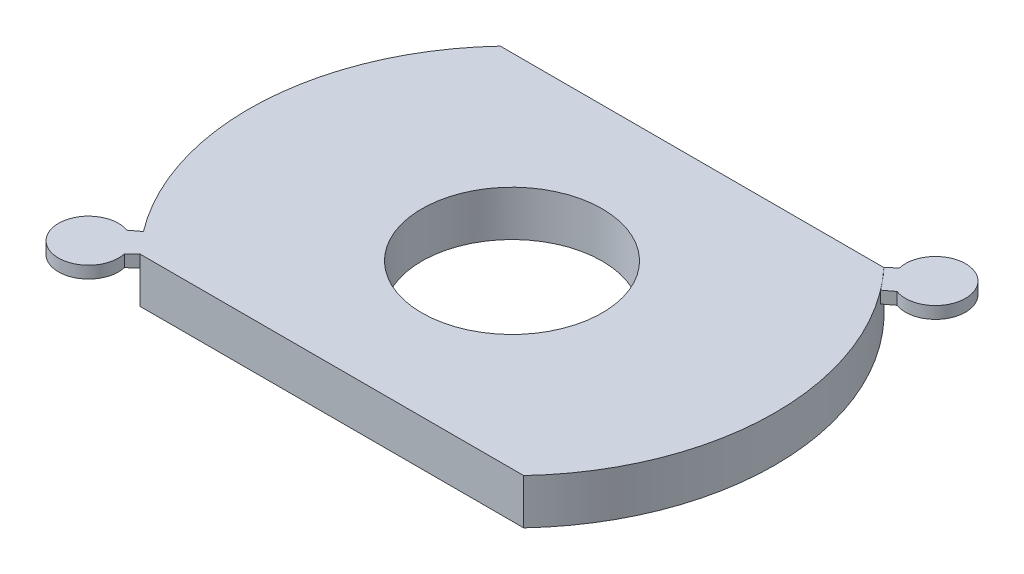
SolidWorks part; units mm, degrees
material "1345 Alloy"
ref_plane "Front Plane" through (0, 0, 0) normal (0, 0, 1) x (1, 0, 0)
ref_plane "Top Plane" through (0, 0, 0) normal (0, 1, 0) x (1, 0, 0)
ref_plane "Right Plane" through (0, 0, 0) normal (1, 0, 0) x (0, 0, -1)
sketch "Sketch1" plane through (0, 0, 0) normal (0, 1, 0) x (1, 0, 0)
  line L0 (-1712.4333, 578.2677) -> (-1658.0172, 559.892) construction
  line L1 (-1682.6566, 611.2885) -> (-1644.8226, 597.5438) construction
  line L2 (-1769.951, 660.0706) -> (-1712.4333, 741.8735) construction
  circle A0 centre (0, 0) radius 1750
  arc A3 (-1712.4333, 578.2677) -> (-1712.4333, 741.8735) centre (-1769.951, 660.0706) cw construction
  arc A4 (-1712.4333, 741.8735) -> (-1682.6566, 611.2885) centre (-1769.951, 660.0706) cw construction
extrude "Boss-Extrude1" add sketch "Sketch1" along normal blind 500
sketch "Sketch2" plane through (0, 500, 0) normal (0, 1, 0) x (1, 0, 0)
  circle A0 centre (0, 0) radius 900
extrude "Cut-Extrude2" cut sketch "Sketch2" against normal blind 300
sketch "Sketch9" plane through (0, 0, 0) normal (0, -1, 0) x (1, 0, 0)
  line L1 (-2106.3119, -1198.0599) -> (2106.3119, -1198.0599)
  line L2 (-2106.3119, -1198.0599) -> (-2106.3119, 1198.0599)
  line L3 (-2106.3119, 1198.0599) -> (2106.3119, 1198.0599)
  line L4 (2106.3119, -1198.0599) -> (2106.3119, 1198.0599)
  line L5 (-2106.3119, -1198.0599) -> (2106.3119, 1198.0599) construction
  line L6 (-2106.3119, 1198.0599) -> (2106.3119, -1198.0599) construction
  line L7 (-2636.6179, -2082.9122) -> (2636.6179, -2082.9122)
  line L8 (-2636.6179, -2082.9122) -> (-2636.6179, 2082.9122)
  line L9 (-2636.6179, 2082.9122) -> (2636.6179, 2082.9122)
  line L10 (2636.6179, -2082.9122) -> (2636.6179, 2082.9122)
  line L11 (-2636.6179, -2082.9122) -> (2636.6179, 2082.9122) construction
  line L12 (-2636.6179, 2082.9122) -> (2636.6179, -2082.9122) construction
  point P0 (0, 0)
  point P6 (0, 0)
extrude "Cut-Extrude10" cut sketch "Sketch9" against normal through all both and the other way through all
sketch "Sketch3" plane through (0, 0, 0) normal (0, -1, 0) x (1, 0, 0)
  circle A0 centre (0, 0) radius 600
extrude "Cut-Extrude3" cut sketch "Sketch3" against normal blind 300
shell "Shell1" thickness 1.5 removed face at (0, 0, -600)
sketch "Sketch10" plane through (0, 198.5, 0) normal (0, -1, 0) x (1, 0, 0)
  line L1 (2226.5426, -1551.0392) -> (-2226.5426, -1551.0392)
  line L2 (2226.5426, -1551.0392) -> (2226.5426, 1551.0392)
  line L3 (2226.5426, 1551.0392) -> (-2226.5426, 1551.0392)
  line L4 (-2226.5426, -1551.0392) -> (-2226.5426, 1551.0392)
  line L5 (2226.5426, -1551.0392) -> (-2226.5426, 1551.0392) construction
  line L6 (2226.5426, 1551.0392) -> (-2226.5426, -1551.0392) construction
  point P0 (0, 0)
extrude "Cut-Extrude11" cut sketch "Sketch10" along normal through all
sketch "Sketch12" plane through (0, 500, 0) normal (0, 1, 0) x (1, 0, 0)
  line L0 (-1275.7204, -1197.9305) -> (-1329.4274, -1248.3625)
  line L1 (-1275.7204, -1197.9305) -> (-1329.4274, -1248.3625)
  line L2 (-1456.8867, -1104.0663) -> (-1394.7434, -1056.9725)
  line L3 (-1212.6439, -1163.1539) -> (-1394.7434, -1056.9725) construction
  line L4 (-1329.4274, -1248.3625) -> (-1275.8583, -1198.0599) construction
  line L5 (1275.5989, -1198.0599) -> (-1275.5989, -1198.0599) construction
  line L6 (-1275.5989, 1198.0599) -> (1275.5989, -1198.0599) construction
  line L7 (0, 0) -> (-1750, 0) construction
  line L13 (0, 0) -> (0, 1750) construction
  line L14 (1212.6439, 1163.1539) -> (1394.7434, 1056.9725) construction
  line L15 (1329.4274, 1248.3625) -> (1275.8583, 1198.0599) construction
  line L16 (1275.7204, 1197.9305) -> (1329.4274, 1248.3625)
  line L17 (1275.7204, 1197.9305) -> (1329.4274, 1248.3625)
  line L18 (1456.8867, 1104.0663) -> (1394.7434, 1056.9725)
  arc A0 (-1275.5989, -1198.0599) -> (-1524.5473, -859.2179) centre (0, 0) cw
  arc A1 (-1275.7204, 1197.9305) -> (-1275.5989, 1198.0599) centre (0, 0) ccw construction
  arc A2 (-1329.4274, -1248.3625) -> (-1456.8867, -1104.0663) centre (-1524.5473, -1292.2737) cw
  arc A3 (-1275.7204, -1197.9305) -> (-1275.5989, -1198.0599) centre (0, 0) cw construction
  arc A4 (1275.8583, 1198.0599) -> (1394.7434, 1056.9725) centre (24.3381, 22.854) cw
  arc A6 (1329.4274, 1248.3625) -> (1456.8867, 1104.0663) centre (1524.5473, 1292.2737) cw
  arc M6 (-1275.5989, 1198.0599) -> (-1275.5989, -1198.0599) centre (0, 0) ccw
extrude "Boss-Extrude2" add sketch "Sketch12" against normal blind 80 contours A2 L0 L2 M6 region at (-1511.5348, 500, 1280.7775)
extrude "Boss-Extrude3" add sketch "Sketch12<6>" against normal blind 80 separate body contours A6 L17 A4 L18 region at (1511.5672, 500, -1280.8004)
sketch "Sketch12<6>" plane through (0, 500, 0) normal (0, 1, 0) x (1, 0, 0) same geometry as "Sketch12"
sketch "Sketch13" plane through (0, 200, 0) normal (0, 1, 0) x (1, 0, 0)
  circle A0 centre (0, 0) radius 900 construction
  circle A1 centre (0, 0) radius 900
  circle A2 centre (0, 0) radius 600 construction
  circle A3 centre (0, 0) radius 600
extrude "Boss-Extrude4" add sketch "Sketch13" along normal up to surface (300 mm away) up to face at (0, 500, 900)
sketch "Sketch14" plane through (0, 198.5, 0) normal (0, -1, 0) x (1, 0, 0)
  circle A0 centre (0, 0) radius 901.5 construction
  circle A1 centre (0, 0) radius 901.5
  circle A2 centre (0, 0) radius 601.5
extrude "Cut-Extrude12" cut sketch "Sketch14" against normal up to surface (300 mm away) up to face at (0, 498.5, 901.5)
